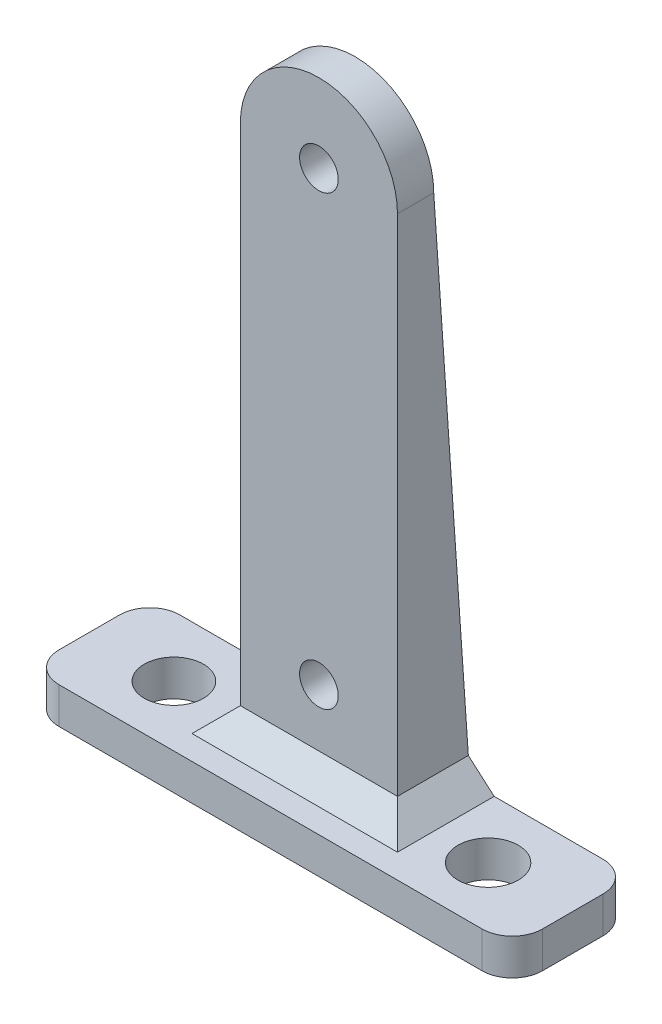
SolidWorks part; units mm, degrees
ref_plane "前视基准面" through (0, 0, 0) normal (0, 0, 1) x (1, 0, 0)
ref_plane "上视基准面" through (0, 0, 0) normal (0, 1, 0) x (1, 0, 0)
ref_plane "右视基准面" through (0, 0, 0) normal (1, 0, 0) x (0, 0, -1)
sketch "草图1" plane through (0, 0, 0) normal (0, 1, 0) x (1, 0, 0)
  line L1 (0, 0) -> (40, 0)
  line L2 (0, 0) -> (0, 10)
  line L3 (0, 10) -> (40, 10)
  line L4 (40, 0) -> (40, 10)
  dimension "D1" = 40
  dimension "D2" = 10
extrude "凸台-拉伸1" add sketch "草图1" along normal blind 3
sketch "草图2" plane through (0, 3, 0) normal (0, 1, 0) x (1, 0, 0)
  line L0 (-3.0519, 5) -> (42.0914, 5) construction
  line L1 (20, 10.6499) -> (20, -3.0532) construction
  line L2 (26.5, 7) -> (13.5, 7)
  line L3 (13.5, 7) -> (13.5, 4)
  line L4 (13.5, 4) -> (26.5, 4)
  line L5 (26.5, 7) -> (26.5, 4)
  line L6 (40, 10) -> (0, 10) construction
  line L7 (0, 10) -> (0, 0) construction
  point P9 (20, 4)
  point P10 (20, 7)
  dimension "D1" = 3
  dimension "D2" = 13
  dimension "D3" = 20
  dimension "D4" = 3
extrude "凸台-拉伸2" add sketch "草图2" along normal blind 43.75
sketch "草图4" plane through (0, 0, -4) normal (0, 0, 1) x (1, 0, 0)
  line L0 (13.5, 46.75) -> (26.5, 46.75) construction
  line L1 (13.5, 46.75) -> (26.5, 46.75)
  arc A0 (26.5, 46.75) -> (13.5, 46.75) centre (20, 46.75) ccw
extrude "凸台-拉伸3" add sketch "草图4" against normal blind 3
sketch "草图5" plane through (13.5, 0, 0) normal (-1, 0, 0) x (0, 0, 1)
  line L0 (-10, 3) -> (-7, 46.75)
rib "筋1" sketch "草图5" sketch "草图5" thickness 2 extrusion direction parallel to sketch draft on no parameters "D1"=2
sketch "草图7" plane through (26.5, 0, 0) normal (1, 0, 0) x (0, 0, -1)
  line L0 (7, 46.75) -> (10, 3)
rib "筋2" sketch "草图7" sketch "草图7" thickness 2 extrusion direction parallel to sketch draft on no parameters "D1"=2
sketch "草图8" plane through (0, 0, -4) normal (0, 0, 1) x (1, 0, 0)
  line L0 (20, -3.9148) -> (20, 53.1577) construction
  line L1 (13.5, 3) -> (26.5, 3) construction
  circle A0 centre (20, 9.75) radius 1.6
  circle A1 centre (20, 46.75) radius 1.6
  point P2 (20, 9.75)
  dimension "D1" = 6.75
extrude "切除-拉伸1" cut sketch "草图8" against normal blind 3
fillet "圆角1" radius 2.5 4 edges at (0, 1.5, -10) (40, 1.5, -10) (40, 1.5, 0) (0, 1.5, 0)
sketch "草图9" plane through (0, 3, 0) normal (0, 1, 0) x (1, 0, 0)
  line L0 (-2.5396, 5) -> (43.4041, 5) construction
  line L1 (7, 14.653) -> (7, -3.1162) construction
  line L2 (33, 14.653) -> (33, -3.1162) construction
  line L3 (0, 7.5) -> (0, 2.5) construction
  line L4 (40, 2.5) -> (40, 7.5) construction
  circle A0 centre (7, 5) radius 2.45
  circle A1 centre (33, 5) radius 2.5
  dimension "D1" = 7
  dimension "D2" = 7
extrude "切除-拉伸5" cut sketch "草图9" against normal blind 3
chamfer "倒角2" distance 2 angle 45 3 edges at (20, 3, -4) (26.5, 3, -7) (13.5, 3, -7)
